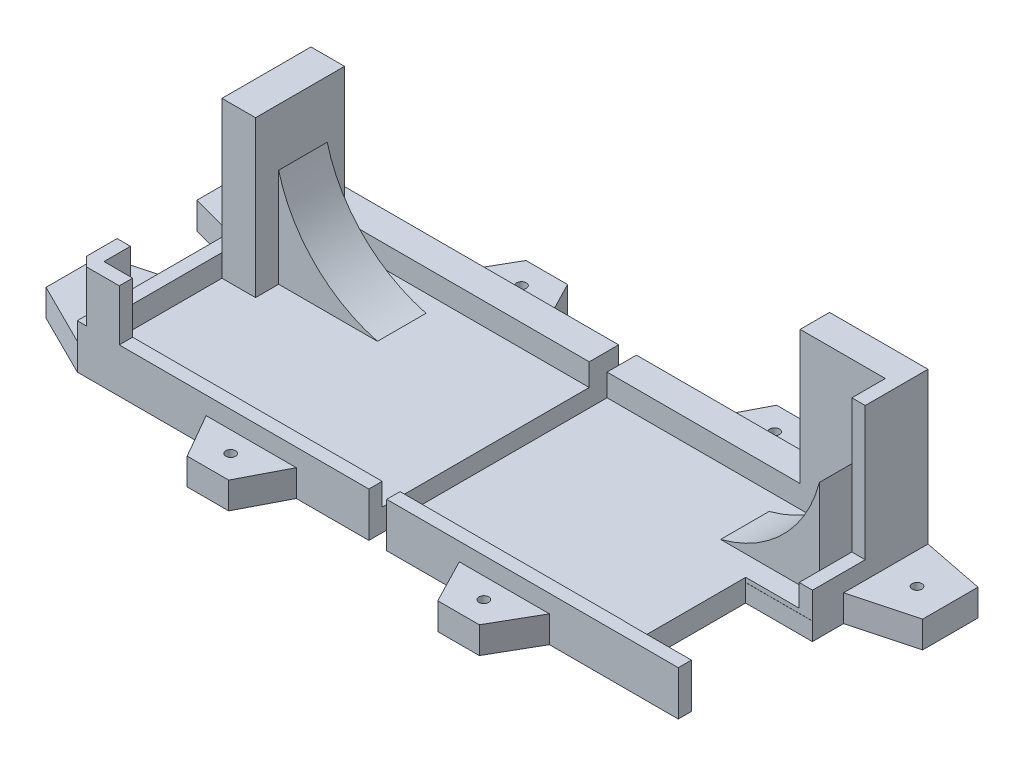
SolidWorks part; units mm, degrees
ref_plane "Front Plane" through (0, 0, 0) normal (0, 0, 1) x (1, 0, 0)
ref_plane "Top Plane" through (0, 0, 0) normal (0, 1, 0) x (1, 0, 0)
ref_plane "Right Plane" through (0, 0, 0) normal (1, 0, 0) x (0, 0, -1)
sketch "Sketch1" plane through (0, 0, 0) normal (0, 0, 1) x (1, 0, 0)
  line L0 (0, 0) -> (125, 0) construction
  line L1 (55, 0) -> (-55, 0) construction
  line L2 (0, 0) -> (-125, 0) construction
sketch "Sketch2" plane through (0, 0, 0) normal (0, 1, 0) x (1, 0, 0)
  line L0 (0, 0) -> (0, 146.5205) construction
  line L1 (-129, -27.1) -> (129, -27.1)
  line L2 (-129, -27.1) -> (-129, 65.9)
  line L3 (-129, 65.9) -> (129, 65.9)
  line L4 (129, -27.1) -> (129, 65.9)
  line L5 (0, -102.4582) -> (0, 102.4582) construction
  point P0 (0, 0)
  point P10 (0, 65.9)
  dimension "D1" = 129
  dimension "D2" = 27.1
  dimension "D3" = 65.9
sketch "Sketch3" plane through (0, 0, 0) normal (0, 1, 0) x (1, 0, 0)
  line L1 (-135, -33.1) -> (135, -33.1)
  line L2 (-135, -33.1) -> (-135, 79.1)
  line L3 (-135, 79.1) -> (135, 79.1)
  line L4 (135, -33.1) -> (135, 79.1)
  point P0 (0, 0)
  dimension "D1" = 270
  dimension "D2" = 112.2
  dimension "D3" = 33.1
extrude "Boss-Extrude1" add sketch "Sketch3" along normal blind 20
extrude "Cut-Extrude1" cut sketch "Sketch2" along normal blind 30 from offset 10
sketch "Sketch4" plane through (0, 0, 0) normal (0, 1, 0) x (1, 0, 0)
  line L1 (-135, -77.1) -> (135, -77.1)
  line L2 (-135, -77.1) -> (-135, 79.1)
  line L3 (-135, 79.1) -> (135, 79.1)
  line L4 (135, -77.1) -> (135, 79.1)
  point P0 (0, 0)
sketch "Sketch5" plane through (135, 0, 0) normal (1, 0, 0) x (0, 0, -1)
  line L0 (0, 0) -> (27.15, 0)
  line L1 (112.7288, 0) -> (-112.7288, 0) construction
  line L2 (0, 80.7562) -> (0, -80.7562) construction
  line L4 (27.15, 0) -> (27.15, 8)
  line L5 (27.15, 8) -> (0, 8)
  line L6 (0, 0) -> (0, 8)
  dimension "D1" = 8
  dimension "D2" = 27.15
extrude "Cut-Extrude2" cut sketch "Sketch5" against normal blind 30
mirror "Mirror1" about plane through (0, 0, 0) normal (0, 0, 1) of "Cut-Extrude2"
sketch "Sketch7" plane through (135, 0, 0) normal (1, 0, 0) x (0, 0, -1)
  line L1 (0, 8) -> (27.2, 8)
  line L2 (0, 8) -> (0, 20)
  line L3 (0, 20) -> (27.2, 20)
  line L4 (27.2, 8) -> (27.2, 20)
  line L5 (-33.1, 20) -> (79.1, 20) construction
  line L6 (0, 0) -> (27.2, 0) construction
  line L7 (-77.1, 0) -> (79.1, 0) construction
  line L8 (27.2, 0) -> (27.2, 20) construction
  dimension "D1" = 27.2
extrude "Cut-Extrude3" cut sketch "Sketch7" against normal blind 30
mirror "Mirror2" about plane through (0, 0, 0) normal (0, 0, 1) of "Cut-Extrude3"
sketch "Sketch23" plane through (0, 20, 0) normal (0, 1, 0) x (1, 0, 0)
  line L12 (-135, 79.1) -> (-135, -33.1) construction
  line L17 (-135, -15.2013) -> (-129, -15.2013)
  line L19 (-129, -15.2013) -> (-129, -27.1)
  line L20 (-129, -27.1) -> (-116.1295, -27.1)
  line L21 (-129, -27.1) -> (105, -27.1) construction
  line L22 (-116.1295, -27.1) -> (-116.1295, -33.1)
  line L23 (-135, -33.1) -> (135, -33.1) construction
  line L24 (-116.1295, -33.1) -> (-130.7488, -33.1)
  line L25 (-130.7488, -33.1) -> (-135, -28.8488)
  line L26 (-135, -28.8488) -> (-135, -15.2013)
  line L27 (-80.7562, 0) -> (80.7562, 0) construction
  dimension "D1" = 15.2013
extrude "Boss-Extrude6" add sketch "Sketch23" along normal blind 23
sketch "Sketch25" plane through (0, 0, 0) normal (0, 1, 0) x (1, 0, 0)
  line L0 (-135, 79.1) -> (-135, -24.7) construction
  line L1 (-135, -24.7) -> (-163, -24.7) construction
  line L2 (-163, -24.7) -> (-163, 79.1) construction
  line L3 (-163, 79.1) -> (-135, 79.1) construction
  line L4 (-135, -24.7) -> (-163, -19.1464)
  line L5 (-163, -19.1464) -> (-163, 5.7447)
  line L6 (-163, 5.7447) -> (-135, 13.2009)
  line L8 (-163, 79.1) -> (-163, -24.7) construction
  line L9 (-135, 79.1) -> (-163, 79.1) construction
  line L10 (-163, 48.6553) -> (-135, 41.1991)
  line L11 (-163, 73.5464) -> (-163, 48.6553)
  line L12 (-135, 79.1) -> (-163, 73.5464)
  line L13 (-77.113, -33.1) -> (135, -33.1) construction
  line L14 (135, -33.1) -> (135, -53.1) construction
  line L15 (135, -77.1) -> (135, 79.1) construction
  line L16 (77.113, -33.1) -> (65.6215, -53.1)
  line L17 (65.6215, -53.1) -> (46.9579, -53.1)
  line L18 (46.9579, -53.1) -> (36.6201, -33.1)
  line L20 (-46.9579, -53.1) -> (-36.6201, -33.1)
  line L21 (-65.6215, -53.1) -> (-46.9579, -53.1)
  line L22 (-77.113, -33.1) -> (-65.6215, -53.1)
  line L23 (-116.1295, -33.1) -> (135, -33.1) construction
  line L24 (135, -53.1) -> (-114.7581, -53.1) construction
  line L25 (-135, 41.1991) -> (-135, 79.1)
  line L26 (36.6201, -33.1) -> (77.113, -33.1)
  line L27 (-135, 13.2009) -> (-135, -24.7)
  line L28 (-77.113, -33.1) -> (-36.6201, -33.1)
  dimension "D1" = 28
  dimension "D2" = 20
  dimension "D3" = 103.8
  dimension "D4" = 154.226
  dimension "D5" = 93.9158
sketch "Sketch26" plane through (0, 0, 0) normal (0, 1, 0) x (1, 0, 0)
  line L0 (-135, 41.1991) -> (-135, 79.1)
  line L1 (-135, 79.1) -> (-163, 73.5464)
  line L2 (-163, 73.5464) -> (-163, 48.6553)
  line L3 (-163, 48.6553) -> (-135, 41.1991)
  line L4 (-135, 13.2009) -> (-163, 5.7447)
  line L5 (-163, 5.7447) -> (-163, -19.1464)
  line L6 (-163, -19.1464) -> (-135, -33.1)
  line L7 (-135, -33.1) -> (-135, 13.2009)
  line L8 (-77.113, -33.1) -> (-36.6201, -33.1)
  line L9 (-36.6201, -33.1) -> (-46.9579, -53.1)
  line L10 (-46.9579, -53.1) -> (-65.6215, -53.1)
  line L11 (-65.6215, -53.1) -> (-77.113, -33.1)
  line L12 (36.6201, -33.1) -> (77.113, -33.1)
  line L13 (77.113, -33.1) -> (65.6215, -53.1) construction
  line L14 (36.6201, -33.1) -> (46.9579, -53.1)
  line L15 (46.9579, -53.1) -> (65.6215, -53.1)
  line L16 (65.6215, -53.1) -> (77.113, -33.1)
  line L17 (36.6201, -33.1) -> (36.6201, 79.1) construction
  line L18 (36.6201, 79.1) -> (36.6201, 23) construction
  line L19 (36.6201, 23) -> (-144.3099, 23) construction
  line L20 (65.6215, 99.1) -> (77.113, 79.1)
  line L21 (46.9579, 99.1) -> (65.6215, 99.1)
  line L22 (36.6201, 79.1) -> (46.9579, 99.1)
  line L23 (36.6201, 79.1) -> (77.113, 79.1)
  line L24 (-65.6215, 99.1) -> (-77.113, 79.1)
  line L25 (-46.9579, 99.1) -> (-65.6215, 99.1)
  line L26 (-36.6201, 79.1) -> (-46.9579, 99.1)
  line L27 (-77.113, 79.1) -> (-36.6201, 79.1)
  line L28 (-135, 79.1) -> (135, 79.1) construction
  line L29 (-135, 79.1) -> (135, 79.1) construction
  line L30 (135, 79.1) -> (0, 79.1) construction
  line L31 (0, 79.1) -> (0, -106.5527) construction
  line L32 (0, -102.4582) -> (0, 102.4582) construction
  line L33 (163, 48.6553) -> (135, 41.1991)
  line L34 (163, 73.5464) -> (163, 48.6553)
  line L35 (135, 79.1) -> (163, 73.5464)
  line L36 (135, 41.1991) -> (135, 79.1)
extrude "Boss-Extrude7" add sketch "Sketch26" along normal blind 12
sketch "Sketch27" plane through (0, 12, 0) normal (0, 1, 0) x (1, 0, 0)
  line L0 (-135, -33.1) -> (-135, 13.2009) construction
  line L1 (-135, 13.2009) -> (-135, -9.9495) construction
  line L2 (-135, -9.9495) -> (-176.2766, -9.9495) construction
  line L3 (-135, 41.1991) -> (-135, 79.1) construction
  line L4 (-135, 79.1) -> (-135, 60.1495) construction
  line L5 (-135, 60.1495) -> (-175.0712, 60.1495) construction
  line L6 (-77.113, -33.1) -> (-36.6201, -33.1) construction
  line L7 (-36.6201, -33.1) -> (-56.8666, -33.1) construction
  line L8 (-56.8666, -33.1) -> (-56.8666, -66.7762) construction
  line L9 (36.6201, -33.1) -> (77.113, -33.1) construction
  line L10 (77.113, -33.1) -> (56.8666, -33.1) construction
  line L11 (56.8666, -33.1) -> (56.8666, -65.8523) construction
  line L12 (-56.8666, -42.31) -> (82.7467, -42.31) construction
  line L13 (56.8666, -33.1) -> (56.8666, -42.31) construction
  line L14 (-135, 60.1495) -> (-149.003, 60.1495) construction
  line L15 (-149.003, 60.1495) -> (-149.003, -39.8818) construction
  line L16 (-135, -9.9495) -> (-149.003, -9.9495) construction
  line L17 (-36.6201, -33.1) -> (-36.6201, 79.1) construction
  line L18 (-135, 79.1) -> (135, 79.1) construction
  line L19 (-36.6201, 79.1) -> (-36.6201, 23) construction
  line L20 (-36.6201, 23) -> (58.6506, 23) construction
  line L21 (56.8666, 79.1) -> (56.8666, 88.31) construction
  line L22 (-56.8666, 88.31) -> (82.7467, 88.31) construction
  line L23 (56.8666, 79.1) -> (56.8666, 111.8523) construction
  line L24 (77.113, 79.1) -> (56.8666, 79.1) construction
  line L25 (36.6201, 79.1) -> (77.113, 79.1) construction
  line L26 (-56.8666, 79.1) -> (-56.8666, 112.7762) construction
  line L27 (-36.6201, 79.1) -> (-56.8666, 79.1) construction
  line L28 (-77.113, 79.1) -> (-36.6201, 79.1) construction
  line L29 (-135, 79.1) -> (135, 79.1) construction
  line L30 (135, 79.1) -> (0, 79.1) construction
  line L31 (0, 79.1) -> (0, -137.5547) construction
  line L32 (0, -102.4582) -> (0, 102.4582) construction
  line L33 (135, 60.1495) -> (149.003, 60.1495) construction
  line L34 (135, 60.1495) -> (175.0712, 60.1495) construction
  line L35 (135, 79.1) -> (135, 60.1495) construction
  line L36 (135, 41.1991) -> (135, 79.1) construction
  circle A0 centre (-56.8666, -42.31) radius 2.1825
  circle A1 centre (56.8666, -42.31) radius 2.1825
  circle A2 centre (-149.003, 60.1495) radius 2.1825
  circle A3 centre (-149.003, -9.9495) radius 2.1825
  circle A4 centre (56.8666, 88.31) radius 2.1825
  circle A5 centre (-56.8666, 88.31) radius 2.1825
  circle A6 centre (149.003, 60.1495) radius 2.1825
  dimension "D1" = 4.365
  dimension "D2" = 4.365
  dimension "D3" = 4.365
  dimension "D4" = 4.365
extrude "Cut-Extrude4" cut sketch "Sketch27" against normal blind 12
sketch "Sketch30" plane through (0, 10, 0) normal (0, 1, 0) x (1, 0, 0)
  line L0 (-129, -27.1) -> (121, -27.2) construction
  line L1 (105, -27.2) -> (135, -27.2) construction
  line L2 (121, -27.2) -> (121, 65.8) construction
  line L4 (129, 27.2) -> (121, 27.2)
  line L5 (129, 27.2) -> (129, 65.8)
  line L6 (129, 65.8) -> (121, 65.8)
  line L7 (121, 27.2) -> (121, 65.8)
  dimension "D1" = 250
  dimension "D2" = 93
sketch "Sketch31" plane through (0, 0, -65.9) normal (0, 0, 1) x (1, 0, 0)
  line L0 (0, 0) -> (0, 10) construction
  line L2 (66.6024, 72) -> (120.7328, 41.7693) construction
  line L3 (0, 10) -> (120.7328, 7.9269) construction
  line L4 (129, 10) -> (-129, 10) construction
  line L7 (0, 10) -> (0, 30) construction
  line L8 (129, 20) -> (-129, 20) construction
  line L9 (0, 30) -> (120.5861, 20) construction
  line L11 (120.7328, 41.7693) -> (129, 10)
  line L12 (129, 10) -> (66.6024, 10)
  line L15 (-4, 10) -> (0, 10) construction
  line L16 (-129, 41.7693) -> (-129, 10)
  line L17 (-129, 10) -> (-74.8695, 10)
  line L19 (-74.8695, 10) -> (-74.8695, 72) construction
  line L20 (120.7328, 7.9269) -> (120.7328, 41.7693) construction
  line L21 (0, 10) -> (129, 10) construction
  line L22 (129, 10) -> (129, 41.7693) construction
  arc A0 (66.6024, 10) -> (120.7328, 41.7693) centre (66.6024, 72) ccw
  arc A1 (-74.8695, 10) -> (-129, 41.7693) centre (-74.8695, 72) cw
  dimension "D4" = 62
  dimension "D1" = 10
  dimension "D3" = 121
sketch "Sketch32" plane through (0, 0, -65.9) normal (0, 0, 1) x (1, 0, 0)
  line L0 (0, 0) -> (0, 10) construction
  line L1 (-129, 10) -> (121, 10) construction
  line L2 (0, -102.4582) -> (0, 102.4582) construction
  line L3 (0, 10) -> (129, 10) construction
  line L4 (129, 10) -> (-129, 10) construction
  line L5 (129, 10) -> (129, 63.2477) construction
  line L6 (0, 10) -> (7.54, 10) construction
  line L7 (129, 54.3797) -> (69.0001, 70.0007) construction
  line L8 (84.618, 10) -> (129, 10)
  line L9 (129, 10) -> (129, 54.3797)
  line L10 (84.618, 10) -> (69.0001, 70.0007) construction
  line L11 (7.54, 10) -> (7.54, 26.033) construction
  line L12 (-69.538, 10) -> (-113.92, 10)
  line L13 (-113.92, 10) -> (-113.92, 54.3797)
  line L14 (84.618, 10) -> (84.618, 127.1267) construction
  line L15 (84.618, 127.1267) -> (0, 127.1267) construction
  line L16 (0, 127.1267) -> (-107.7705, 127.1267) construction
  line L17 (-69.538, 10) -> (-69.538, 127.1267) construction
  line L18 (69.0001, 70.0007) -> (69.0001, 10) construction
  arc A0 (84.618, 10) -> (129, 54.3797) centre (69.0001, 70.0007) ccw
  arc A1 (-69.538, 10) -> (-113.92, 54.3797) centre (-53.9201, 70.0007) cw
  dimension "D1" = 7.54
  dimension "D2" = 62
  dimension "D3" = 60.817
  dimension "D4" = 14.59
  dimension "D5" = 117.1267
extrude "Boss-Extrude10" add sketch "Sketch32" along normal blind 21.8 from offset 7.8
sketch "Sketch34" plane through (0, 10, 0) normal (0, 1, 0) x (1, 0, 0)
  line L0 (-113.92, 58.1) -> (-113.92, 65.9) construction
  line L1 (129, 65.9) -> (-129, 65.9) construction
  line L2 (-113.92, 65.9) -> (-129, 65.9) construction
  line L3 (-113.92, 58.1) -> (-113.92, 25.9) construction
  line L5 (-129, 65.9) -> (-113.92, 65.9)
  line L6 (-129, 65.9) -> (-129, 25.9)
  line L7 (-129, 25.9) -> (-113.92, 25.9)
  line L8 (-113.92, 65.9) -> (-113.92, 25.9)
  dimension "D1" = 40
extrude "Boss-Extrude11" add sketch "Sketch34" along normal blind 70
sketch "Sketch36" plane through (0, 20, 0) normal (0, 1, 0) x (1, 0, 0)
  line L0 (135, 79.1) -> (135, 50.8891)
  line L1 (135, 50.8891) -> (129, 50.8891)
  line L2 (129, 36.3) -> (129, 58.1) construction
  line L3 (129, 50.8891) -> (129, 65.9)
  line L4 (129, 65.9) -> (90.7458, 65.9)
  line L5 (129, 65.9) -> (-113.92, 65.9) construction
  line L6 (90.7458, 65.9) -> (90.7458, 79.1)
  line L7 (135, 79.1) -> (-135, 79.1) construction
  line L8 (90.7458, 79.1) -> (135, 79.1)
extrude "Boss-Extrude12" add sketch "Sketch36" along normal blind 60
sketch "Sketch38" plane through (0, 0, 0) normal (0, 0, 1) x (1, 0, 0)
  line L0 (0, 0) -> (4, 0) construction
  line L1 (0, 0) -> (125, 0) construction
  line L2 (4, 0) -> (4, 28.1015) construction
  line L3 (4, 28.1015) -> (-4, 28.1015) construction
  line L4 (-4, 28.1015) -> (-4, 0) construction
  line L5 (0, 0) -> (-125, 0) construction
  line L6 (-4, 0) -> (4, 0) construction
  line L8 (4, 0) -> (-4, 0)
  line L9 (4, 0) -> (4, 28.1015)
  line L10 (4, 28.1015) -> (-4, 28.1015)
  line L11 (-4, 0) -> (-4, 28.1015)
  dimension "D1" = 4
  dimension "D2" = 8
extrude "Cut-Extrude5" cut sketch "Sketch38" against normal through all both and the other way through all
